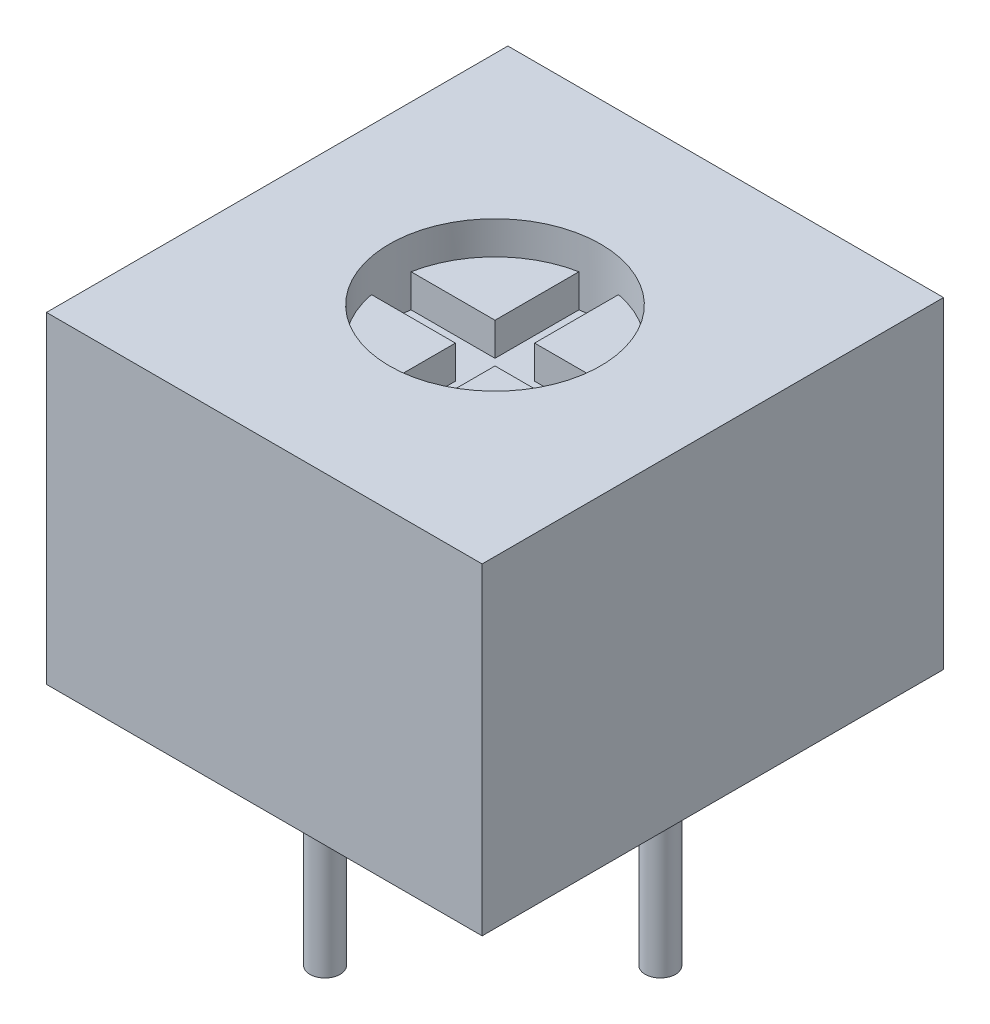
SolidWorks part; units mm, degrees
ref_plane "Front" through (0, 0, 0) normal (0, 0, 1) x (1, 0, 0)
ref_plane "Top" through (0, 0, 0) normal (0, 1, 0) x (1, 0, 0)
ref_plane "Right" through (0, 0, 0) normal (1, 0, 0) x (0, 0, -1)
sketch "Эскиз1" plane through (0, 0, 0) normal (0, 1, 0) x (1, 0, 0)
  line L0 (-0.3, 1.5716) -> (-0.3, 0.3)
  line L1 (3.3, -3.495) -> (-3.3, -3.495)
  line L2 (3.3, -3.495) -> (3.3, 3.495)
  line L3 (3.3, 3.495) -> (-3.3, 3.495)
  line L4 (-3.3, -3.495) -> (-3.3, 3.495)
  line L5 (3.3, -3.495) -> (-3.3, 3.495) construction
  line L6 (3.3, 3.495) -> (-3.3, -3.495) construction
  line L7 (-0.3, 0.3) -> (-1.5716, 0.3)
  line L8 (0, 1.9469) -> (0, -1.7309) construction
  line L9 (0.3, 1.5716) -> (0.3, 0.3)
  line L10 (0.3, 0.3) -> (1.5716, 0.3)
  line L11 (-1.8124, 0) -> (2.1532, 0) construction
  line L12 (-0.3, -0.3) -> (-1.5716, -0.3)
  line L13 (-0.3, -1.5716) -> (-0.3, -0.3)
  line L14 (0.3, -1.5716) -> (0.3, -0.3)
  line L15 (0.3, -0.3) -> (1.5716, -0.3)
  circle A0 centre (0, 0) radius 1.6
  point P0 (0, 0)
  dimension "D3" = 3.2
  dimension "D1" = 6.99
  dimension "D2" = 6.6
  dimension "D4" = 0.3
  dimension "D5" = 0.3
extrude "Бобышка-Вытянуть1" add sketch "Эскиз1" along normal blind 4.88 contours L4 L1 L2 L3 A0 | L15 A0 L10 L9 L0 L7 L12 L13 L14 | L14 A0 L15 | L12 A0 L13 | L0 A0 L7 | L10 A0 L9 region at (0, 0, 0) region at (-0.8096, 0, -0.8096) region at (0.8096, 0, -0.8096) region at (-0.8096, 0, 0.8096) region at (0.8096, 0, 0.8096) region at (0, 0, 3.3989)
extrude "Вырез-Вытянуть1" cut sketch "Эскиз1<3>" against normal blind 1 from surface contours L15 A0 L10 L9 L0 L7 L12 L13 L14 region at (0, 0, 0) starting at face at (0, 4.88, 0)
sketch "Эскиз1<3>" plane through (0, 0, 0) normal (0, 1, 0) x (1, 0, 0) same geometry as "Эскиз1"
extrude "Вырез-Вытянуть2" cut sketch "Эскиз1<4>" against normal blind 0.5 from surface contours L12 A0 L13 | L0 A0 L7 | L10 A0 L9 | L14 A0 L15 region at (-0.8096, 0, -0.8096) region at (0.8096, 0, -0.8096) region at (-0.8096, 0, 0.8096) region at (0.8096, 0, 0.8096) starting at face at (0, 4.88, 0)
sketch "Эскиз1<4>" plane through (0, 0, 0) normal (0, 1, 0) x (1, 0, 0) same geometry as "Эскиз1"
sketch "Эскиз2" plane through (0, 0, 0) normal (0, -1, 0) x (1, 0, 0)
  line L0 (3.3, -3.495) -> (-3.3, -3.495) construction
  circle A0 centre (0, 2.575) radius 0.23
  circle A1 centre (2.54, 0.035) radius 0.23
  circle A2 centre (-2.54, 0.035) radius 0.23
  point P8 (0, 0)
  point P9 (0, 0)
  dimension "D1" = 0.46
  dimension "D2" = 3.53
  dimension "D3" = 2.54
  dimension "D4" = 2.54
  dimension "D5" = 2.54
extrude "Бобышка-Вытянуть2" add sketch "Эскиз2" along normal blind 2.5
